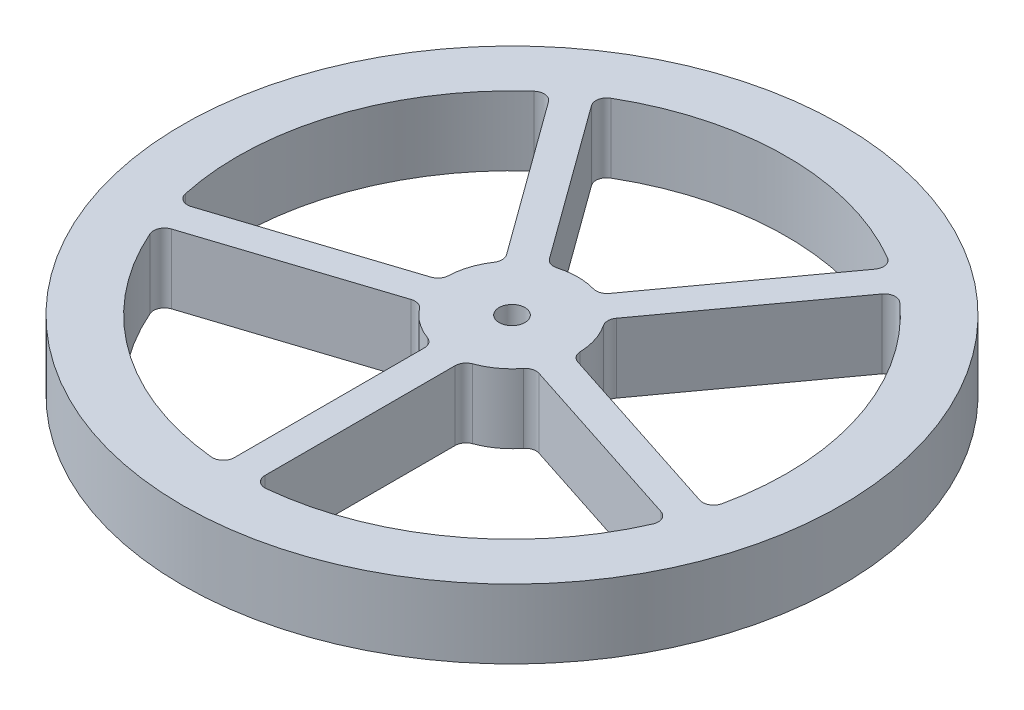
SolidWorks part; units mm, degrees
material "Nylon 6/10"
ref_plane "Front Plane" through (0, 0, 0) normal (0, 0, 1) x (1, 0, 0)
ref_plane "Top Plane" through (0, 0, 0) normal (0, 1, 0) x (1, 0, 0)
ref_plane "Right Plane" through (0, 0, 0) normal (1, 0, 0) x (0, 0, -1)
sketch "Sketch1" plane through (0, 0, 0) normal (0, 1, 0) x (1, 0, 0)
  circle A0 centre (0, 0) radius 38.1
  circle A1 centre (0, 0) radius 1.5
  dimension "D1" = 76.2
  dimension "D2" = 3
extrude "Boss-Extrude1" add sketch "Sketch1" along normal blind 8
sketch "Sketch2" plane through (0, 8, 0) normal (0, 1, 0) x (1, 0, 0)
  circle A0 centre (0, 0) radius 7.62
  circle A1 centre (0, 0) radius 31.75
  circle A3 centre (0, 0) radius 38.1 construction
  dimension "D1" = 15.24
  dimension "D2" = 6.35
extrude "Cut-Extrude1" cut sketch "Sketch2" against normal up to surface (8 mm away) up to face at (0, 0, 38.1)
sketch "Sketch3" plane through (0, 8, 0) normal (0, 1, 0) x (1, 0, 0)
  line L0 (-1.778, -8.3512) -> (-1.778, -30.3272)
  line L1 (1.778, -8.3512) -> (1.778, -30.3272)
  line L3 (0, -7.62) -> (0, -31.75) construction
  line L4 (-1.778, -19.3392) -> (0, -19.685) construction
  line L5 (0, -19.685) -> (1.778, -19.3392) construction
  circle A0 centre (0, 0) radius 7.62 construction
  circle A1 centre (0, 0) radius 31.75 construction
  arc A2 (-3.175, -31.5909) -> (3.175, -31.5909) centre (0, 0) ccw
  arc A3 (-2.6126, -7.1581) -> (2.6126, -7.1581) centre (0, 0) ccw
  arc A4 (-3.175, -31.5909) -> (-1.778, -30.3272) centre (-3.048, -30.3272) ccw
  arc A5 (1.778, -30.3272) -> (3.175, -31.5909) centre (3.048, -30.3272) ccw
  arc A6 (-2.6126, -7.1581) -> (-1.778, -8.3512) centre (-3.048, -8.3512) cw
  arc A7 (1.778, -8.3512) -> (2.6126, -7.1581) centre (3.048, -8.3512) cw
  dimension "D3" = 1.27
  dimension "D4" = 1.27
  dimension "D5" = 1.27
  dimension "D2" = 6.35
extrude "Boss-Extrude2" add sketch "Sketch3" against normal up to surface (8 mm away) contours L0 A4 A2 A5 L1 A7 A3 A6 up to face at (0, 0, 31.75)
ref_axis "Axis1" through (0, 8, 0) along (0, -1, 0)
pattern_circular "CirPattern1" count 5 over 360 about axis through (0, 8, 0) along (0, -1, 0) of "Boss-Extrude2"
